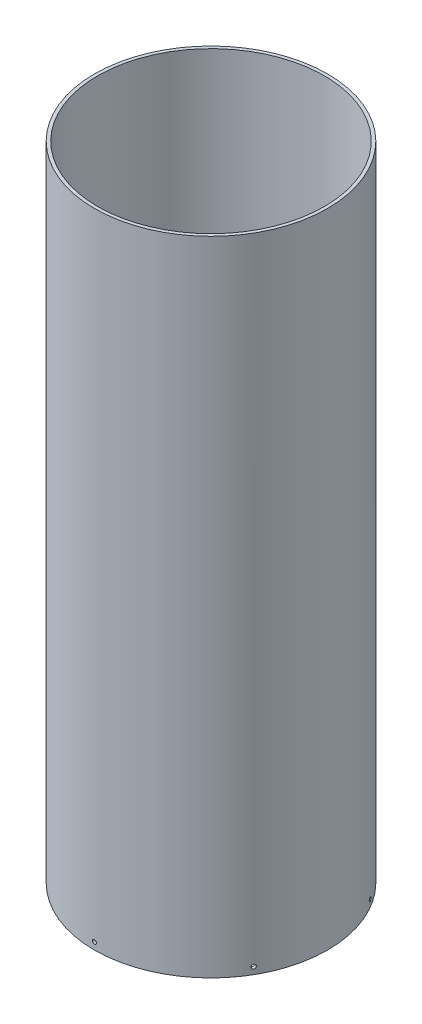
SolidWorks part; units mm, degrees
ref_plane "Front Plane" through (0, 0, 0) normal (0, 0, 1) x (1, 0, 0)
ref_plane "Top Plane" through (0, 0, 0) normal (0, 1, 0) x (1, 0, 0)
ref_plane "Right Plane" through (0, 0, 0) normal (1, 0, 0) x (0, 0, -1)
sketch "Sketch1" plane through (0, 0, 0) normal (0, 1, 0) x (1, 0, 0)
  circle A0 centre (0, 0) radius 76.2
  circle A1 centre (0, 0) radius 78.359
  dimension "D1" = 152.4
  dimension "D2" = 156.718
extrude "Boss-Extrude1" add sketch "Sketch1" along normal blind 431.8
ref_axis "Axis1" through (0, 431.8, 0) along (0, -1, 0)
sketch "Sketch2" plane through (0, 0, 0) normal (0, 0, 1) x (1, 0, 0)
  line L0 (0, 0) -> (0, 4.7625) construction
  circle A0 centre (0, 4.7625) radius 1.3526
  dimension "D1" = 2.7051
  dimension "D2" = 4.7625
extrude "Cut-Extrude1" cut sketch "Sketch2" against normal through all
pattern_circular "CirPattern1" count 6 over 360 about axis through (0, 431.8, 0) along (0, -1, 0) of "Cut-Extrude1"
equation "\"D1@Boss-Extrude1\"=\"Aft_Upper_Length\""
equation "\"AB_Coupling_Section_Length\"= 0.375in"
equation "\"AB_Coupler_Num_Screws\"= 6"
equation "\"AB_Coupling_Screw_Diameter\"= 0.1065in"
equation "\"AB_Coupler_OD_Length\"= 1in"
equation "\"AB_Coupler_Length\"= \"AB_Coupler_OD_Length\" + \"AB_Coupling_Section_Length\" * 2"
equation "\"D1@Sketch2\"=\"AB_Coupling_Screw_Diameter\""
equation "\"D2@Sketch2\"=\"AB_Coupling_Section_Length\"/2"
equation "\"D1@CirPattern1\"=\"AB_Coupler_Num_Screws\""
equation "\"Aft_Section_Length\"= 40in"
equation "\"Aft_Upper_Length\"= \"Aft_Section_Length\" - \"Aft_Lower_Length\" - \"AB_Coupler_OD_Length\""
equation "\"Aft_Lower_Length\"= 22in"
